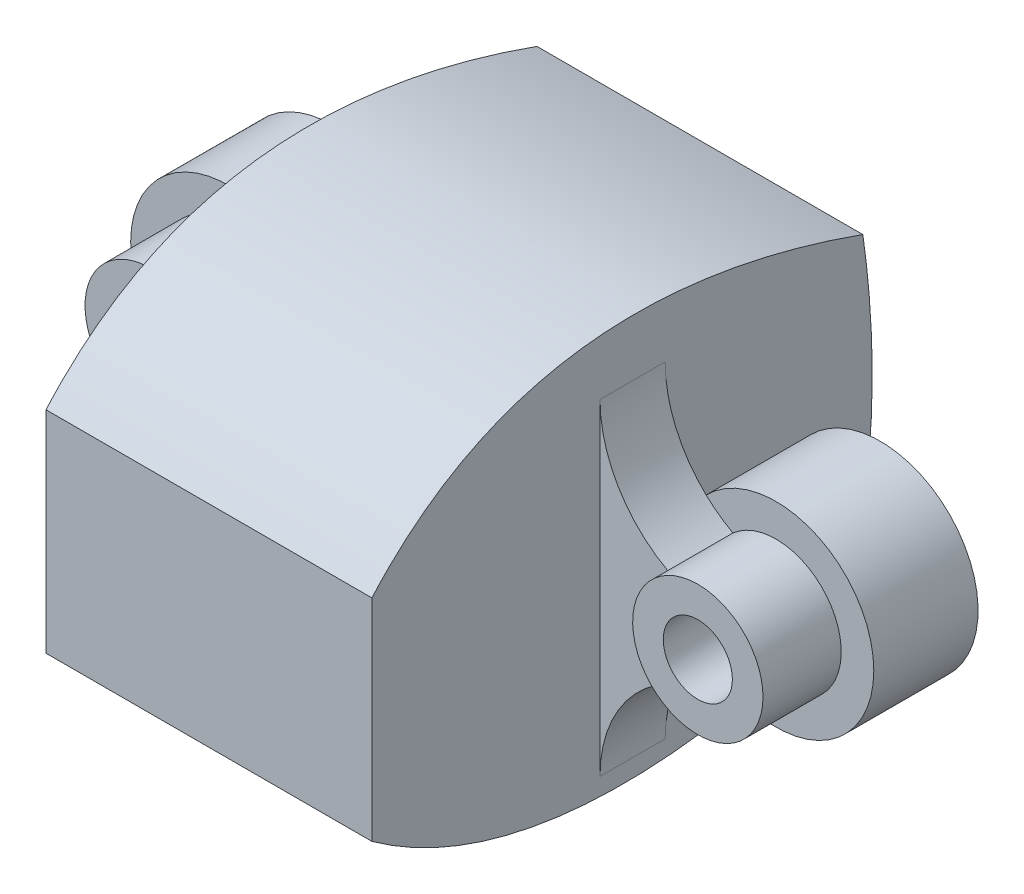
SolidWorks part; units mm, degrees
ref_plane "Front Plane" through (0, 0, 0) normal (0, 0, 1) x (1, 0, 0)
ref_plane "Top Plane" through (0, 0, 0) normal (0, 1, 0) x (1, 0, 0)
ref_plane "Right Plane" through (0, 0, 0) normal (1, 0, 0) x (0, 0, -1)
sketch "Sketch1" plane through (0, 0, 0) normal (1, 0, 0) x (0, 0, -1)
  line L0 (-19.0962, 121.2258) -> (-19.0962, 137.4045)
  spline S0 degree 2 poles (-19.0962, 137.4045) (-6.4675, 151.6991) (18.5686, 142.7118) knots 0 0 0 1 1 1
  spline S1 degree 2 poles (18.5686, 142.7118) (20.5155, 129.0566) (17.199, 118.5721) knots 0 0 0 1 1 1
  spline S2 degree 3 poles (17.199, 118.5721) (7.3552, 114.9342) (-7.5425, 112.8814) (-19.0962, 121.2258) knots 0 0 0 0 1 1 1 1
extrude "Boss-Extrude1" add sketch "Sketch1" along normal mid plane 25
sketch "Sketch3" plane through (0, 0, 0) normal (1, 0, 0) x (0, 0, -1)
  line L0 (0.9038, 129.3152) -> (-19.0962, 129.3152) construction
  line L1 (3.4038, 125.5652) -> (-1.5962, 125.5652)
  line L2 (3.4038, 125.5652) -> (3.4038, 133.0652)
  line L3 (3.4038, 133.0652) -> (-1.5962, 133.0652)
  line L4 (-1.5962, 125.5652) -> (-1.5962, 133.0652)
  line L5 (3.4038, 125.5652) -> (-1.5962, 133.0652) construction
  line L6 (3.4038, 133.0652) -> (-1.5962, 125.5652) construction
  line L7 (-19.0962, 137.4045) -> (-19.0962, 121.2258) construction
  point P4 (0.9038, 129.3152)
  dimension "D1" = 7.5
  dimension "D2" = 5
  dimension "D3" = 20
extrude "Boss-Extrude2" add sketch "Sketch3" along normal mid plane 55
sketch "Sketch4" plane through (0, 0, -3.4038) normal (0, 0, -1) x (-1, 0, 0)
  line L0 (-27.5, 129.3152) -> (27.5, 129.3152) construction
  line L1 (-27.5, 125.5652) -> (-27.5, 133.0652) construction
  line L2 (27.5, 125.5652) -> (27.5, 133.0652) construction
  circle A0 centre (-21.0048, 129.3152) radius 7.5
  circle A1 centre (21.0048, 129.3152) radius 7.5
  dimension "D1" = 15
extrude "Boss-Extrude3" add sketch "Sketch4" along normal blind 8
sketch "Sketch5" plane through (0, 0, -3.4038) normal (0, 0, 1) x (1, 0, 0)
  line L0 (0, 146.1811) -> (0, 115.4028) construction
  line L1 (12.5, 146.1811) -> (-12.5, 146.1811) construction
  line L2 (-12.5, 115.4028) -> (12.5, 115.4028) construction
  line L3 (-21.0048, 136.8152) -> (-31.11, 136.8152)
  line L4 (21.0048, 136.8152) -> (31.11, 136.8152)
  line L5 (21.0048, 136.8152) -> (21.0048, 119.4086)
  line L6 (21.0048, 119.4086) -> (31.11, 119.4086)
  line L7 (31.11, 136.8152) -> (31.11, 119.4086)
  line L8 (21.0048, 136.8152) -> (31.11, 119.4086) construction
  line L9 (21.0048, 119.4086) -> (31.11, 136.8152) construction
  line L10 (-21.0048, 136.8152) -> (-21.0048, 119.4086)
  line L11 (-21.0048, 119.4086) -> (-31.11, 119.4086)
  line L12 (-31.11, 136.8152) -> (-31.11, 119.4086)
  arc A0 (27.5, 133.0652) -> (14.5096, 133.0652) centre (21.0048, 129.3152) ccw construction
  point P10 (26.0574, 128.1119)
extrude "Cut-Extrude1" cut sketch "Sketch5" along normal through all
sketch "Sketch6" plane through (0, 0, -3.4038) normal (0, 0, 1) x (1, 0, 0)
  line L0 (21.0048, 133.0652) -> (21.0048, 125.5652) construction
  line L1 (-21.0048, 125.5652) -> (-21.0048, 133.0652) construction
  circle A0 centre (21.0048, 129.3152) radius 5
  circle A1 centre (-21.0048, 129.3152) radius 5
  dimension "D1" = 10
extrude "Boss-Extrude4" add sketch "Sketch6" along normal blind 6
fillet "Fillet1" radius 10 4 edges at (12.5, 125.5652, -0.9038) (12.5, 133.0652, -0.9038) (-12.5, 133.0652, -0.9038) (-12.5, 125.5652, -0.9038)
sketch "Sketch7" plane through (0, 0, 2.5962) normal (0, 0, 1) x (1, 0, 0)
  circle A0 centre (21.0048, 129.3152) radius 2.65
  circle A1 centre (-21.0048, 129.3152) radius 2.65
  dimension "D1" = 5.3
extrude "Cut-Extrude2" cut sketch "Sketch7" against normal blind 6
ref_plane "Plane1" through (0, 0, -0.9038) normal (0, 0, 1) x (1, 0, 0)
sketch "Sketch8" plane through (0, 0, -0.9038) normal (0, 0, 1) x (1, 0, 0)
  line L0 (21.0048, 129.3152) -> (-21.0048, 129.3152) construction
  point P4 (0, 129.3152)
move or copy body "Body-Move/Copy1" bodies to move or copy 106 copy no translate (0, -129.32, -0.9)
sketch "Sketch10" plane through (0, 0, -4.3038) normal (0, 0, -1) x (-1, 0, 0)
  line L1 (-12.5, 16.8611) -> (12.5, 16.8611)
  line L2 (-12.5, 16.8611) -> (-12.5, -13.9172)
  line L3 (-12.5, -13.9172) -> (12.5, -13.9172)
  line L4 (12.5, 16.8611) -> (12.5, -13.9172)
  line L5 (-12.5, 16.8611) -> (12.5, -13.9172) construction
  line L6 (-12.5, -13.9172) -> (12.5, 16.8611) construction
  point P4 (0, 1.4719)
extrude "Cut-Extrude3" [suppressed] cut sketch "Sketch10" along normal through all
sketch "Sketch11" plane through (0, 0, 0.6962) normal (0, 0, 1) x (1, 0, 0)
  line L0 (12.5, -13.9172) -> (12.5, -8.0942) construction
  line L1 (-12.5, 16.8611) -> (12.5, 16.8611)
  line L2 (-12.5, 16.8611) -> (-12.5, -16.4911)
  line L3 (-12.5, -16.4911) -> (12.5, -16.4911)
  line L4 (12.5, 16.8611) -> (12.5, -16.4911)
  line L5 (-12.5, 16.8611) -> (12.5, -16.4911) construction
  line L6 (-12.5, -16.4911) -> (12.5, 16.8611) construction
  point P4 (0, 0.185)
extrude "Cut-Extrude4" [suppressed] cut sketch "Sketch11" along normal through all
sketch "Sketch12" plane through (0, 0, 0.6962) normal (0, 0, 1) x (1, 0, 0)
  line L1 (-17.6976, 3.7452) -> (17.6976, 3.7452)
  line L2 (-17.6976, 3.7452) -> (-17.6976, 19.0947)
  line L3 (-17.6976, 19.0947) -> (17.6976, 19.0947)
  line L4 (17.6976, 3.7452) -> (17.6976, 19.0947)
  line L5 (-17.6976, 3.7452) -> (17.6976, 19.0947) construction
  line L6 (-17.6976, 19.0947) -> (17.6976, 3.7452) construction
  line L7 (-17.6976, -3.7548) -> (17.6976, -3.7548)
  line L8 (-17.6976, -3.7548) -> (-17.6976, -18.2927)
  line L9 (-17.6976, -18.2927) -> (17.6976, -18.2927)
  line L10 (17.6976, -3.7548) -> (17.6976, -18.2927)
  line L11 (-17.6976, -3.7548) -> (17.6976, -18.2927) construction
  line L12 (-17.6976, -18.2927) -> (17.6976, -3.7548) construction
  point P4 (0, 11.4199)
  point P12 (0, -11.0238)
extrude "Cut-Extrude5" [suppressed] cut sketch "Sketch12" against normal up to surface (5 mm away)
sketch "Sketch13" [suppressed] plane through (0, 0, -4.3038) normal (0, 0, 1) x (1, 0, 0)
  line L0 (17.6976, -3.7548) -> (-17.6976, -3.7548) construction
  line L1 (-17.6976, 3.7452) -> (17.6976, 3.7452) construction
  line L2 (14.5096, 3.7452) -> (17.6976, 3.7452)
  line L3 (17.6976, -3.7548) -> (14.5096, -3.7548)
  line L6 (-17.6976, 3.7452) -> (-14.5096, 3.7452)
  line L7 (-14.5096, -3.7548) -> (-17.6976, -3.7548)
  line L10 (14.5096, -3.7548) -> (-14.5096, -3.7548)
  line L11 (-14.5096, 3.7452) -> (14.5096, 3.7452)
  circle A0 centre (21.0048, -0.0048) radius 2.65 construction
  circle A1 centre (-21.0048, -0.0048) radius 2.65 construction
  arc A2 (14.5096, -3.7548) -> (14.5096, 3.7452) centre (21.0048, -0.0048) ccw
  arc A3 (17.6976, -3.7548) -> (17.6976, 3.7452) centre (21.0048, -0.0048) ccw
  arc A4 (14.5096, -3.7548) -> (14.5096, 3.7452) centre (21.0048, -0.0048) ccw
  arc A6 (-17.6976, 3.7452) -> (-17.6976, -3.7548) centre (-21.0048, -0.0048) ccw
  arc A7 (-14.5096, 3.7452) -> (-14.5096, -3.7548) centre (-21.0048, -0.0048) ccw
  arc A9 (-14.5096, 3.7452) -> (-14.5096, -3.7548) centre (-21.0048, -0.0048) ccw
  circle A10 centre (21.0048, -0.0048) radius 2.65
  circle A11 centre (-21.0048, -0.0048) radius 2.65
  dimension "D1" = 0
  dimension "D2" = 0
extrude "Boss-Extrude5" [suppressed] add sketch "Sketch13" along normal up to surface (6 mm away)
sketch "Sketch14" plane through (0, 0, -4.3038) normal (0, 0, -1) x (-1, 0, 0)
  line L1 (12.5, 12.5165) -> (12.5, -12.5262)
  line L2 (12.5, 12.5165) -> (12.5, -12.5262)
  arc A2 (15.6422, 5.2385) -> (15.6422, -5.2482) centre (21.0048, -0.0048) ccw
  arc A3 (12.5, 12.5165) -> (15.6422, 5.2385) centre (22.5, 12.5165) ccw
  arc A4 (15.6422, 5.2385) -> (15.6422, -5.2482) centre (21.0048, -0.0048) ccw
  arc A7 (12.5, 12.5165) -> (15.6422, 5.2385) centre (22.5, 12.5165) ccw
  arc A8 (15.6422, -5.2482) -> (12.5, -12.5262) centre (22.5, -12.5262) ccw
  arc A9 (15.6422, -5.2482) -> (12.5, -12.5262) centre (22.5, -12.5262) ccw
  dimension "D1" = 0
extrude "Boss-Extrude6" [suppressed] add sketch "Sketch14" along normal up to surface (8 mm away)
sketch "Sketch15" plane through (0, 0, 0.6962) normal (0, 0, 1) x (1, 0, 0)
  line L0 (12.5, 8.0845) -> (12.5, 16.8611) construction
  line L1 (-33.8996, 19.6269) -> (-12.5, 19.6269)
  line L2 (-33.8996, 19.6269) -> (-33.8996, -18.0047)
  line L3 (-33.8996, -18.0047) -> (-12.5, -18.0047)
  line L4 (-12.5, 19.6269) -> (-12.5, -18.0047)
  line L5 (-33.8996, 19.6269) -> (-12.5, -18.0047) construction
  line L6 (-33.8996, -18.0047) -> (-12.5, 19.6269) construction
  line L7 (12.5, 21.39) -> (32.7445, 21.39)
  line L8 (12.5, 21.39) -> (12.5, -18.0047)
  line L9 (12.5, -18.0047) -> (32.7445, -18.0047)
  line L10 (32.7445, 21.39) -> (32.7445, -18.0047)
  line L11 (12.5, 21.39) -> (32.7445, -18.0047) construction
  line L12 (12.5, -18.0047) -> (32.7445, 21.39) construction
  line L13 (-12.5, 16.8611) -> (-12.5, 8.0845) construction
  point P4 (-23.1998, 0.8111)
  point P9 (22.6222, 1.6926)
extrude "Cut-Extrude6" [suppressed] cut sketch "Sketch15" against normal through all both and the other way through all
